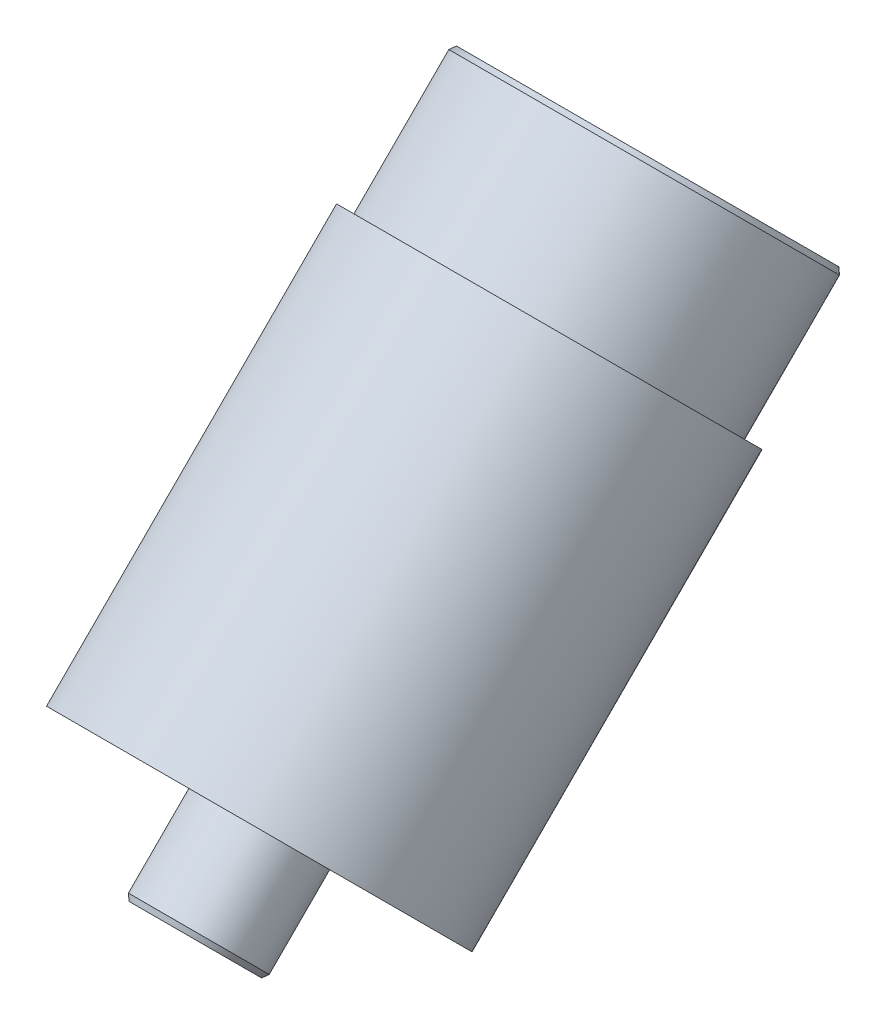
SolidWorks part; units mm, degrees
ref_plane "Front Plane" through (0, 0, 0) normal (0, 0, 1) x (1, 0, 0)
ref_plane "Top Plane" through (0, 0, 0) normal (0, 1, 0) x (1, 0, 0)
ref_plane "Right Plane" through (0, 0, 0) normal (1, 0, 0) x (0, 0, -1)
sketch3d "3DSketch1" plane through (0, 0, 0) normal (0, 0, 1) x (1, 0, 0)
  dimension "D1" = 45
sketch "Sketch4" plane through (0, -5.3655, 5.3655) normal (0, 0.7071, -0.7071) x (-1, 0, 0)
  circle A0 centre (0, 0) radius 25
  circle A1 centre (0, 0) radius 23
  dimension "D1" = 50
  dimension "D2" = 46
extrude "Boss-Extrude7" add sketch "Sketch4" along normal blind 9 and the other way blind 50 separate body
sketch "Sketch7" plane through (0, 0, 0) normal (0, 1, 0) x (1, 0, 0)
  line L1 (-98.8562, -56.9274) -> (98.8562, -56.9274)
  line L2 (-98.8562, -56.9274) -> (-98.8562, 56.9274)
  line L3 (-98.8562, 56.9274) -> (98.8562, 56.9274)
  line L4 (98.8562, -56.9274) -> (98.8562, 56.9274)
  line L5 (-98.8562, -56.9274) -> (98.8562, 56.9274) construction
  line L6 (-98.8562, 56.9274) -> (98.8562, -56.9274) construction
  point P0 (0, 0)
sketch3d "3DSketch4" plane through (0, 0, 0) normal (0, 0, 1) x (1, 0, 0)
  dimension "D1" = 13
sketch3d "3DSketch6" plane through (0, 0, 0) normal (0, 0, 1) x (1, 0, 0)
sketch "Sketch20" plane through (0, -40.7208, 40.7208) normal (0, -0.7071, 0.7071) x (1, 0, 0)
  line L0 (0, 0) -> (44.0473, 0) construction
  line L1 (0, 0) -> (0, 37.9743) construction
  line L2 (-2.0199, 1.54) -> (2.0199, 1.54)
  line L9 (-2.0199, -1.54) -> (2.0199, -1.54)
  circle A0 centre (0, 0) radius 25
  circle A1 centre (0, 0) radius 8.275
  arc A2 (-2.0199, 1.54) -> (-2.0199, -1.54) centre (0, 0) ccw
  arc A3 (2.0199, -1.54) -> (2.0199, 1.54) centre (0, 0) ccw
  dimension "D1" = 16.55
  dimension "D2" = 5.08
  dimension "D5" = 1.54
  dimension "D3" = 1.54
extrude "Boss-Extrude16" add sketch "Sketch20" along normal blind 13 separate body contours A1
sketch3d "3DSketch8" plane through (0, 0, 0) normal (0, 0, 1) x (1, 0, 0)
sketch "Sketch24" plane through (0, -49.9132, 49.9132) normal (0, -0.7071, 0.7071) x (1, 0, 0)
  circle A0 centre (0, 0) radius 2.54
  dimension "D1" = 5.08
extrude "Cut-Extrude10" cut sketch "Sketch24" against normal blind 4
extrude "Boss-Extrude17" add sketch "Sketch20<17>" against normal blind 4 contours A0
sketch "Sketch20<17>" plane through (0, -40.7208, 40.7208) normal (0, -0.7071, 0.7071) x (1, 0, 0) same geometry as "Sketch20"
extrude "Cut-Extrude9" cut sketch "Sketch20<15>" along normal blind 30 and the other way blind 30 contours L2 A3 L9 A2
sketch "Sketch20<15>" plane through (0, -40.7208, 40.7208) normal (0, -0.7071, 0.7071) x (1, 0, 0) same geometry as "Sketch20"
sketch "Sketch26" plane through (0, 0.9985, -0.9985) normal (0, 0.7071, -0.7071) x (1, 0, 0)
  line L0 (-98.8562, 40.2538) -> (98.8562, -40.2538) construction
  circle A0 centre (0, 0) radius 22.95
  circle A1 centre (0, 0) radius 21
  dimension "D1" = 42
  dimension "D2" = 45.9
extrude "Boss-Extrude18" add sketch "Sketch26" along normal blind 20 and the other way blind 15
sketch "Sketch27" plane through (0, 0.9985, -0.9985) normal (0, 0.7071, -0.7071) x (1, 0, 0)
  circle A0 centre (0, 0) radius 25
  circle A1 centre (0, 0) radius 21
extrude "Boss-Extrude19" add sketch "Sketch27" against normal blind 15
chamfer "Chamfer1" distance 0.7 angle 35 1 edges at (0, 31.3687, 1.0875) first distance on face at (0, 17.2266, 15.2296)
chamfer "Chamfer2" distance 0.7 angle 35 1 edges at (0, -55.7645, 44.0619) first distance on face at (0, -55.7645, 44.0619)
equation "\"Bearing height\"= 13mm"
equation "\"Bearing inside diameter\"= 16.55mm"
equation "\"Hole for wires\"= \"Bearing inside diameter\" - 6mm"
equation "\"Bearing support diameter\"= \"Bearing inside diameter\" + 4mm"
equation "\"Bearing support height\"= 5mm"
equation "\"Bearing flange height\"= 2mm"
equation "\"D1@Sketch20\"=\"Bearing inside diameter\""
equation "\"Stepper motor shaft diameter\"= 5.08mm"
equation "\"Stepper motor key size\"= 3.08mm"
equation "\"D2@Sketch20\"=\"Stepper motor shaft diameter\""
equation "\"D1@Boss-Extrude16\"=\"Bearing height\""
equation "\"D5@Sketch20\"=\"Stepper motor key size\"/2"
equation "\"D3@Sketch20\"=\"Stepper motor key size\"/2"
equation "\"D1@Sketch24\"=\"Stepper motor shaft diameter\""
equation "\"Stepper motor key height\"= 4mm"
equation "\"D1@Cut-Extrude10\"=\"Stepper motor key height\""
equation "\"D1@Sketch26\"=42mm"
